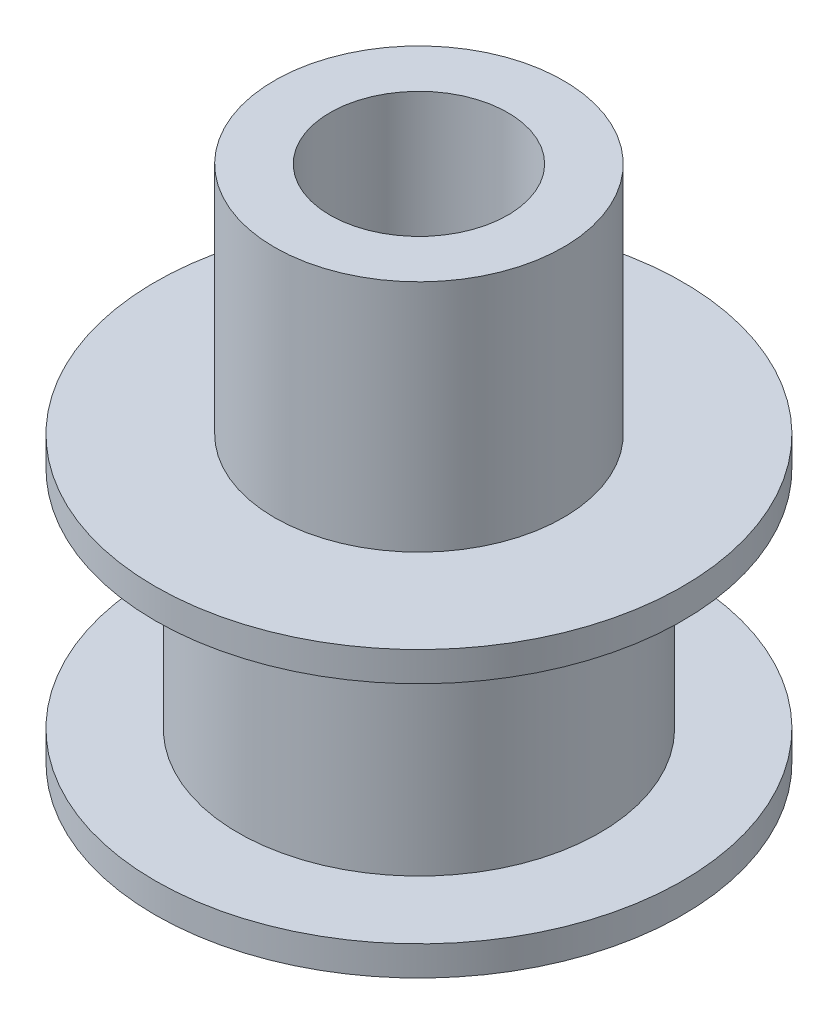
SolidWorks part; units mm, degrees
ref_plane "Front Plane" through (0, 0, 0) normal (0, 0, 1) x (1, 0, 0)
ref_plane "Top Plane" through (0, 0, 0) normal (0, 1, 0) x (1, 0, 0)
ref_plane "Right Plane" through (0, 0, 0) normal (1, 0, 0) x (0, 0, -1)
sketch "Sketch1" plane through (0, 0, 0) normal (0, 1, 0) x (1, 0, 0)
  circle A0 centre (0, 0) radius 8.9
  dimension "D1" = 17.8
extrude "Boss-Extrude1" add sketch "Sketch1" along normal blind 1
sketch "Sketch2" plane through (0, 1, 0) normal (0, 1, 0) x (1, 0, 0)
  circle A0 centre (0, 0) radius 6.1
  dimension "D1" = 12.2
extrude "Boss-Extrude2" add sketch "Sketch2" along normal blind 7.6
sketch "Sketch3" plane through (0, 8.6, 0) normal (0, 1, 0) x (1, 0, 0)
  circle A0 centre (0, 0) radius 8.9 construction
  circle A1 centre (0, 0) radius 8.9
extrude "Boss-Extrude3" add sketch "Sketch3" along normal blind 1
sketch "Sketch4" plane through (0, 9.6, 0) normal (0, 1, 0) x (1, 0, 0)
  circle A0 centre (0, 0) radius 4.875
  dimension "D1" = 9.75
extrude "Boss-Extrude4" add sketch "Sketch4" along normal offset from surface (7.9 mm away) 17.5 up to face at (0, 0, 8.9)
sketch "Sketch5" plane through (0, 17.5, 0) normal (0, 1, 0) x (1, 0, 0)
  circle A0 centre (0, 0) radius 3
  dimension "D1" = 6
extrude "Cut-Extrude1" cut sketch "Sketch5" against normal up to next
